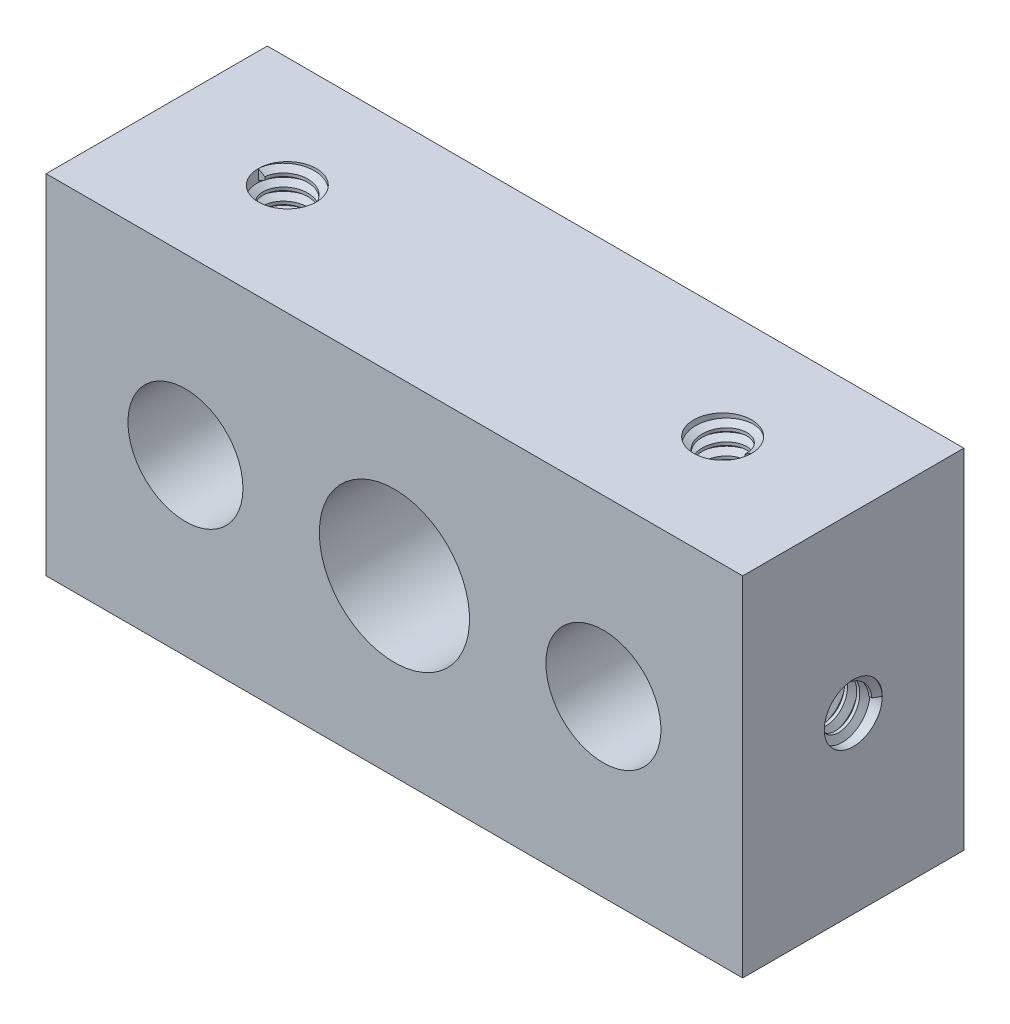
SolidWorks part; units mm, degrees
ref_plane "Front Plane" through (0, 0, 0) normal (0, 0, 1) x (1, 0, 0)
ref_plane "Top Plane" through (0, 0, 0) normal (0, 1, 0) x (1, 0, 0)
ref_plane "Right Plane" through (0, 0, 0) normal (1, 0, 0) x (0, 0, -1)
sketch "Sketch2" plane through (0, 0, 0) normal (0, 1, 0) x (1, 0, 0)
  line L0 (-20, 0) -> (20, 0) construction
  line L1 (-20, 6.35) -> (20, 6.35)
  line L2 (-20, 6.35) -> (-20, -6.35)
  line L3 (-20, -6.35) -> (20, -6.35)
  line L4 (20, 6.35) -> (20, -6.35)
  point P4 (0, 0)
  point P7 (12.5, 0)
  point P9 (-12.5, 0)
  dimension "D1" = 40
  dimension "D2" = 12.7
  dimension "D3" = 12.5
  dimension "D4" = 12.5
extrude "Boss-Extrude1" add sketch "Sketch2" along normal blind 20
hole_wizard "Tap Drill for M4x0.7 Tap1" positions "Sketch3" profile "Sketch4" hole size "M4x0.7" standard "ANSI Metric"
sketch "Sketch3" plane through (0, 0, 0) normal (0, -1, 0) x (-1, 0, 0)
  point P0 (-12.5, 0)
  point P3 (12.5, 0)
  dimension "D1" = 12.5
sketch "Sketch4" plane through (12.5, 0, 0) normal (1, 0, 0) x (0, 0, -1)
  line L0 (0, 0) -> (0, 5.9914)
  line L1 (0, 5.9914) -> (1.65, 5)
  line L2 (1.65, 5) -> (1.65, 0)
  line L5 (1.65, 0) -> (0, 0)
  line L10 (0, 5.9914) -> (-1.65, 5) construction
  line L11 (0, -6.35) -> (0, 107.95) construction
  dimension "Hole Dia." = 3.3
  dimension "Hole Depth" = 5
  dimension "Drill Angle" = 118
sketch "Sketch5" plane through (0, 0, -6.35) normal (0, 0, -1) x (-1, 0, 0)
  line L0 (-12, 10) -> (12, 10) construction
  line L1 (20, 0) -> (-20, 0) construction
  point P0 (-12, 10)
  point P1 (12, 10)
  point P6 (0, 10)
  dimension "D1" = 10
  dimension "D2" = 12
hole_wizard "Ø1.0mm Dowel Hole1" positions "Sketch6" profile "Sketch7" hole size "Ø1.0" standard "ANSI Metric"
sketch "Sketch6" plane through (0, 0, -6.35) normal (0, 0, -1) x (-1, 0, 0)
  line L0 (-12, 10) -> (12, 10) construction
  point P0 (0, 10)
sketch "Sketch7" plane through (0, 10, -6.35) normal (1, 0, 0) x (0, 1, 0)
  line L0 (0, 0) -> (0, 20.5907)
  line L1 (0, 20.5907) -> (4.3116, 18)
  line L2 (4.3116, 18) -> (4.3116, 0)
  line L5 (4.3116, 0) -> (0, 0)
  line L10 (0, 20.5907) -> (-4.3117, 18) construction
  line L11 (0, -6.35) -> (0, 107.95) construction
  dimension "Hole Dia." = 8.6233
  dimension "Hole Depth" = 18
  dimension "Drill Angle" = 118
sketch "Sketch8" plane through (-20, 0, 0) normal (-1, 0, 0) x (0, 0, 1)
  line L0 (-6.35, 10) -> (6.35, 10) construction
  line L1 (-6.35, 20) -> (-6.35, 0) construction
  line L2 (6.35, 20) -> (6.35, 0) construction
  circle A0 centre (0, 10) radius 1.666
  point P6 (0, 10)
  dimension "D1" = 3.332
extrude "Cut-Extrude1" cut sketch "Sketch8" against normal blind 8
thread "Thread2" pitch 0.7 start angle 0, offset 0, length 8, pitch 0.7, diameter 3.332
ref_plane "Plane3" through (-20, 10, -1.666) normal (0, -1, 0) x (0, 0, -1)
sketch "Thread Profile3" plane through (-20, 10, -1.666) normal (0, -1, 0) x (0, 0, -1)
  line L0 (0, 0) -> (0, 0.7) construction
  line L11 (0, 0) -> (0, 0.6125)
  line L12 (0, 0.6125) -> (-0.3789, 0.3937)
  line L13 (-0.3789, 0.3937) -> (-0.3789, 0.2187)
  line L15 (-0.3789, 0.2187) -> (0, 0)
  line L17 (-0.3789, 0.3062) -> (0, 0.3062) construction
  point P2 (0, 0)
  dimension "Pitch" = 0.7
  dimension "Profile_Angle" = 60
  dimension "Profile_Land" = 0.175
  dimension "Profile_Height" = 0.3789
mirror "Mirror3" about plane through (0, 0, 0) normal (1, 0, 0) of "Cut-Extrude1", "Thread2"
sketch "Sketch9" plane through (0, 20, 0) normal (0, 1, 0) x (1, 0, 0)
  line L0 (-12.5, 0) -> (12.5, 0) construction
  point P3 (0, 0)
  point P4 (-12.5, 0)
  point P5 (12.5, 0)
  dimension "D1" = 25
hole_wizard "Tap Drill for M4 Tap1" positions "Sketch10" profile "Sketch11" hole size "M4" standard "ISO"
sketch "Sketch10" plane through (0, 20, 0) normal (0, 1, 0) x (1, 0, 0)
  point P0 (-12.5, 0)
  point P3 (12.5, 0)
sketch "Sketch11" plane through (-12.5, 20, 0) normal (1, 0, 0) x (0, 0, 1)
  line L0 (0, 0) -> (0, 5.826)
  line L1 (0, 5.826) -> (1.666, 4.825)
  line L2 (1.666, 4.825) -> (1.666, 0)
  line L5 (1.666, 0) -> (0, 0)
  line L10 (0, 5.826) -> (-1.666, 4.825) construction
  line L11 (0, -6.35) -> (0, 107.95) construction
  dimension "Hole Dia." = 3.332
  dimension "Hole Depth" = 4.825
  dimension "Drill Angle" = 118
thread "Thread3" pitch 0.7 profile "Thread Profile4" start angle 0, offset 0, length 2.825, pitch 0.7, diameter 3.332
ref_plane "Plane4" through (-14.166, 20, 0) normal (0, 0, 1) x (-1, 0, 0)
sketch "Thread Profile4" plane through (-14.166, 20, 0) normal (0, 0, 1) x (-1, 0, 0)
  line L0 (0, 0) -> (0, 0.7) construction
  line L11 (0, 0) -> (0, 0.6125)
  line L12 (0, 0.6125) -> (-0.3789, 0.3937)
  line L13 (-0.3789, 0.3937) -> (-0.3789, 0.2187)
  line L15 (-0.3789, 0.2187) -> (0, 0)
  line L17 (-0.3789, 0.3062) -> (0, 0.3062) construction
  point P2 (0, 0)
  dimension "Pitch" = 0.7
  dimension "Profile_Angle" = 60
  dimension "Profile_Land" = 0.175
  dimension "Profile_Height" = 0.3789
mirror "Mirror4" about plane through (0, 0, 0) normal (1, 0, 0) of "Thread3"
sketch "Sketch14" plane through (0, 0, -6.35) normal (0, 0, -1) x (-1, 0, 0)
  line L0 (0, 10) -> (-12, 10) construction
  circle A0 centre (-12, 10) radius 3.302
  circle A1 centre (0, 10) radius 4.3116 construction
  dimension "D2" = 6.604
  dimension "D1" = 12
extrude "Cut-Extrude2" cut sketch "Sketch14" against normal through all
mirror "Mirror5" about plane through (0, 0, 0) normal (1, 0, 0) of "Cut-Extrude2"
thread "Thread4" pitch 0.7 profile "Thread Profile5" start angle 0, offset 0, length 0, pitch 0.7, diameter 3.3
ref_plane "Plane5" through (14.15, 0, 0) normal (0, 0, 1) x (1, 0, 0)
sketch "Thread Profile5" plane through (14.15, 0, 0) normal (0, 0, 1) x (1, 0, 0)
  line L0 (0, 0) -> (0, 0.7) construction
  line L11 (0, 0) -> (0, 0.6125)
  line L12 (0, 0.6125) -> (-0.3789, 0.3937)
  line L13 (-0.3789, 0.3937) -> (-0.3789, 0.2187)
  line L15 (-0.3789, 0.2187) -> (0, 0)
  line L17 (-0.3789, 0.3062) -> (0, 0.3062) construction
  point P2 (0, 0)
  dimension "Pitch" = 0.7
  dimension "Profile_Angle" = 60
  dimension "Profile_Land" = 0.175
  dimension "Profile_Height" = 0.3789
mirror "Mirror6" about plane through (0, 0, 0) normal (1, 0, 0) of "Thread4"
equation "\"H\" = 12"
equation "\"D\" = 6.604"
equation "\"D2@Sketch14\"=\"D\""
equation "\"D1@Sketch14\"=\"H\""
